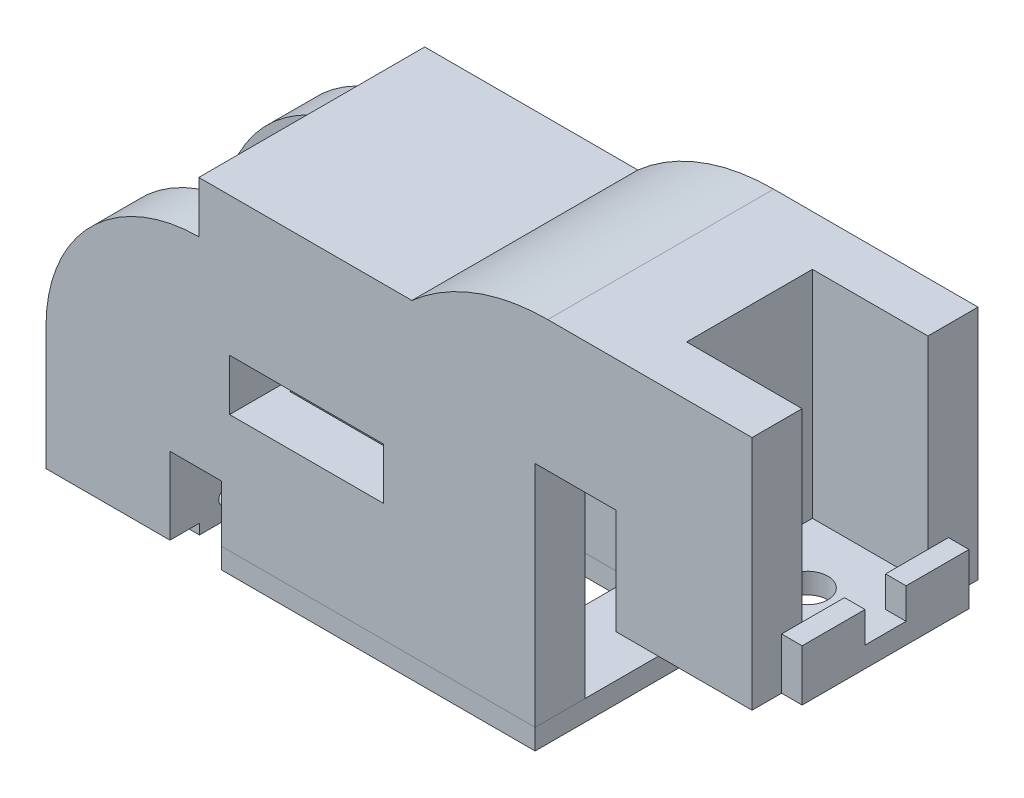
SolidWorks part; units mm, degrees
other "Markup1"
sketch "Sketch12" plane through (-23.815, 32, -11) normal (0, 1, 0) x (1, 0, 0)
ref_plane "Front Plane" through (0, 0, 0) normal (0, 0, 1) x (1, 0, 0)
ref_plane "Top Plane" through (0, 0, 0) normal (0, 1, 0) x (1, 0, 0)
ref_plane "Right Plane" through (0, 0, 0) normal (1, 0, 0) x (0, 0, -1)
sketch "Sketch1" plane through (0, 0, 0) normal (0, 1, 0) x (1, 0, 0)
  line L1 (23.815, -11) -> (-23.815, -11)
  line L2 (23.815, -11) -> (23.815, 11)
  line L3 (23.815, 11) -> (-23.815, 11)
  line L4 (-23.815, -11) -> (-23.815, 11)
  line L5 (23.815, -11) -> (-23.815, 11) construction
  line L6 (23.815, 11) -> (-23.815, -11) construction
  line L7 (10.69, 6.125) -> (15.94, 6.125)
  line L8 (10.69, 6.125) -> (10.69, -6.125)
  line L9 (10.69, -6.125) -> (15.94, -6.125)
  line L10 (15.94, 6.125) -> (15.94, -6.125)
  point P0 (0, 0)
  point P10 (15.94, 0)
  point P11 (23.815, 0)
  point P13 (13.315, 6.125)
  dimension "D1" = 22
  dimension "D2" = 47.63
  dimension "D3" = 10.5
  dimension "D4" = 12.25
  dimension "D5" = 5.25
extrude "Boss-Extrude1" add sketch "Sketch1" along normal blind 2
sketch "Sketch2" plane through (0, 2, 0) normal (0, 1, 0) x (1, 0, 0)
  line L0 (23.815, -11) -> (23.815, 11) construction
  line L1 (-4.935, 6.125) -> (23.815, 6.125)
  line L2 (-4.935, 6.125) -> (-4.935, -6.125)
  line L3 (-4.935, -6.125) -> (23.815, -6.125)
  line L4 (23.815, 6.125) -> (23.815, -6.125)
  point P6 (23.815, 0)
  dimension "D1" = 28.75
  dimension "D2" = 12.25
sketch "Sketch3" plane through (0, 2, 0) normal (0, 1, 0) x (1, 0, 0)
  line L0 (23.815, -11) -> (23.815, 11) construction
  line L1 (-8.935, 11) -> (23.815, 11)
  line L2 (-8.935, 11) -> (-8.935, -11)
  line L3 (-8.935, -11) -> (23.815, -11)
  line L4 (23.815, 11) -> (23.815, -11)
  line L5 (-4.935, 6.125) -> (-4.935, -6.125) construction
  line L8 (23.815, 11) -> (-23.815, 11) construction
  line L9 (-23.815, -11) -> (23.815, -11) construction
  dimension "D1" = 4
extrude "Boss-Extrude2" add sketch "Sketch3" along normal blind 30
extrude "Cut-Extrude1" cut sketch "Sketch2" along normal blind 22.25 contours L3 L4 L1 L2
sketch "Sketch18" plane through (0, 2, 0) normal (0, 1, 0) x (1, 0, 0)
  line L0 (-23.815, 11) -> (-23.815, -11) construction
  line L1 (-23.815, 6.125) -> (-12.565, 6.125)
  line L2 (-23.815, 6.125) -> (-23.815, -6.125)
  line L3 (-23.815, -6.125) -> (-12.565, -6.125)
  line L4 (-12.565, 6.125) -> (-12.565, -6.125)
  line L5 (-8.935, 11) -> (-8.935, -11) construction
  line L6 (-23.815, 11) -> (-8.935, 11)
  line L7 (-23.815, 11) -> (-23.815, -11)
  line L8 (-23.815, -11) -> (-8.935, -11)
  line L9 (-8.935, 11) -> (-8.935, -11)
  circle A0 centre (-18.19, 0) radius 2
  point P6 (-12.565, 0)
  point P12 (-18.19, 6.125)
  line M10 (-8.935, -11) -> (-8.935, 11)
  line M11 (-8.935, 11) -> (-23.815, 11)
  line M12 (-23.815, 11) -> (-23.815, -11)
  line M13 (-23.815, -11) -> (-8.935, -11)
  dimension "D3" = 4
  dimension "D1" = 12.25
  dimension "D2" = 11.25
extrude "Boss-Extrude7" add sketch "Sketch18" along normal blind 25 contours L1 L4 L3 M12 M13 M10 M11 region at (-23.5494, 2, -8.5625)
sketch "Sketch19" plane through (-23.815, 0, 0) normal (-1, 0, 0) x (0, 0, 1)
  line L0 (-11, 0) -> (11, 0) construction
  line L1 (-8.125, 2) -> (8.125, 2)
  line L2 (-8.125, 2) -> (-8.125, 0)
  line L3 (-8.125, 0) -> (8.125, 0)
  line L4 (8.125, 2) -> (8.125, 0)
  line L7 (-6.125, 2) -> (6.125, 2) construction
  line L8 (-6.125, 27) -> (-6.125, 2) construction
  line L9 (6.125, 27) -> (6.125, 2) construction
  dimension "D1" = 2
  dimension "D2" = 2
extrude "Boss-Extrude8" add sketch "Sketch19" along normal blind 2
sketch "Sketch20" plane through (0, 2, 0) normal (0, 1, 0) x (1, 0, 0)
  line L1 (-25.815, 8.125) -> (-23.815, 8.125)
  line L2 (-25.815, 8.125) -> (-25.815, -8.125)
  line L3 (-25.815, -8.125) -> (-23.815, -8.125)
  line L4 (-23.815, 8.125) -> (-23.815, -8.125)
extrude "Boss-Extrude9" add sketch "Sketch20" along normal blind 3
sketch "Sketch39" plane through (-25.815, 0, 0) normal (-1, 0, 0) x (0, 0, 1)
  line L0 (-6.125, 27) -> (-6.125, 5) construction
  line L1 (-6.125, 27) -> (-6.125, 5)
  line L2 (-8.125, 5) -> (8.125, 5) construction
  line L3 (-2, 5) -> (2, 5)
  line L4 (-2, 5) -> (-2, 2)
  line L5 (-2, 2) -> (2, 2)
  line L8 (0, -55) -> (0, 55) construction
  line L9 (2, 5) -> (2, 2)
  line L11 (6.125, 2) -> (-6.125, 2) construction
  line L12 (6.125, 2) -> (-6.125, 2)
  line M9 (-8.125, 0) -> (8.125, 0)
  line M13 (8.125, 5) -> (-8.125, 5)
  dimension "D1" = 4.125
extrude "Cut-Extrude16" cut sketch "Sketch39" against normal blind 2 contours L9 L4 M13 M9 region at (-25.815, 3.5, 0)
sketch "Sketch24" plane through (-25.815, 0, 0) normal (-1, 0, 0) x (0, 0, 1)
  line L0 (-8.125, 0) -> (8.125, 0) construction
  line L2 (-8.125, 0) -> (-8.125, -1)
  line L3 (-8.125, -1) -> (-4.875, -1)
  line L4 (-4.875, 0) -> (-4.875, -1)
  line L16 (0, -55) -> (0, 55) construction
  line L18 (-8.125, 0) -> (-8.125, 0.25)
  line L19 (-8.125, 0.25) -> (-4.875, 0.25)
  line L20 (-4.875, 0) -> (-4.875, 0.25)
  line L21 (8.125, 0) -> (8.125, 0.25)
  line L22 (8.125, 0.25) -> (4.875, 0.25)
  line L23 (4.875, 0) -> (4.875, 0.25)
  line L24 (4.875, 0) -> (4.875, -1)
  line L25 (8.125, -1) -> (4.875, -1)
  line L26 (8.125, 0) -> (8.125, -1)
  dimension "D1" = 1
  dimension "D2" = 3.25
  dimension "D3" = 0.25
extrude "Boss-Extrude11" add sketch "Sketch24" against normal blind 28.03
sketch "Sketch10" plane through (0, 0, 0) normal (0, -1, 0) x (1, 0, 0)
  line L0 (-23.815, 11) -> (23.815, 11) construction
  line L1 (-6.745, 11) -> (-11.745, 11)
  line L2 (-6.745, 11) -> (-6.745, -11)
  line L3 (-6.745, -11) -> (-11.745, -11)
  line L4 (-11.745, 11) -> (-11.745, -11)
  line L5 (23.815, -11) -> (-23.815, -11) construction
  line L6 (-4.935, -6.125) -> (-4.935, 6.125) construction
  line L7 (-4.935, -6.125) -> (-4.935, 6.125)
  line M3 (23.815, 11) -> (-23.815, 11)
  line M11 (-23.815, -11) -> (23.815, -11)
  line M35 (-23.815, 8.125) -> (2.215, 8.125)
  line M37 (2.215, -8.125) -> (-23.815, -8.125)
  line M39 (2.215, 4.875) -> (-25.815, 4.875)
  line M40 (-25.815, -4.875) -> (2.215, -4.875)
  dimension "D1" = 5
  dimension "D2" = 1.81
extrude "Cut-Extrude6" cut sketch "Sketch10" against normal blind 7.5 contours L4 L3 L2 L1
sketch "Sketch21" plane through (-6.745, 0, 0) normal (-1, 0, 0) x (0, 0, 1)
  line L0 (0, -18.15) -> (0, 18.15) construction
  line L1 (11, 0) -> (8.125, 0) construction
  line L2 (11, 7.5) -> (11, 0) construction
  circle A1 centre (5.5, 1) radius 0.75
  circle A2 centre (-5.5, 1) radius 0.75
  dimension "D4" = 1.5
  dimension "D1" = 5.5
  dimension "D2" = 1
extrude "Cut-Extrude12" cut sketch "Sketch21" against normal blind 10
extrude "Cut-Extrude13" cut sketch "Sketch21<5>" along normal through all
sketch "Sketch21<5>" plane through (-6.745, 0, 0) normal (-1, 0, 0) x (0, 0, 1) same geometry as "Sketch21"
extrude "Cut-Extrude14" cut sketch "Sketch10<3>" along normal through all contours L4 L2 M37 M11 | L4 L2 M40 M37 | L4 L2 M39 M40 | L4 L2 M35 M39 | L4 L2 M3 M35 region at (-9.245, 0, 9.5625) region at (-9.245, 0, 6.5) region at (-9.245, 0, 0) region at (-9.245, 0, -6.5) region at (-9.245, 0, -9.5625)
sketch "Sketch10<3>" plane through (0, 0, 0) normal (0, -1, 0) x (1, 0, 0) same geometry as "Sketch10"
sketch "Sketch25" plane through (0, 0, 11) normal (0, 0, 1) x (1, 0, 0)
  line L1 (-5.935, 18.5) -> (9.065, 18.5)
  line L2 (-5.935, 18.5) -> (-5.935, 13.5)
  line L3 (-5.935, 13.5) -> (9.065, 13.5)
  line L4 (9.065, 18.5) -> (9.065, 13.5)
  line L6 (23.815, 32) -> (23.815, 0) construction
  line L7 (-4.935, 24.25) -> (-4.935, 2) construction
  line L8 (-4.935, 24.25) -> (-4.935, 2)
  point P8 (9.065, 16)
  point P13 (23.815, 16)
  dimension "D1" = 5
  dimension "D2" = 15
  dimension "D3" = 1
extrude "Cut-Extrude15" cut sketch "Sketch25" against normal through all contours L1 L8 L3 L4 | L8 L1 L2 L3 region at (-5.435, 16, 11) region at (2.065, 16, 11)
fillet "Fillet2" radius 15 1 edges at (-23.815, 27, 8.5625)
sketch "Sketch29" plane through (0, 32, 0) normal (0, 1, 0) x (1, 0, 0)
  line L0 (23.815, 11) -> (-8.935, 11) construction
  line L1 (23.815, -11) -> (33.69, -11)
  line L2 (23.815, -11) -> (23.815, 11)
  line L3 (23.815, 11) -> (33.69, 11)
  line L4 (33.69, -11) -> (33.69, 11)
  line L5 (-8.935, -11) -> (23.815, -11) construction
  line L6 (23.815, -11) -> (23.815, 11) construction
  dimension "D1" = 9.875
extrude "Boss-Extrude12" add sketch "Sketch29" against normal blind 7.75 contours L3 L4 L1 L2
sketch "Sketch30" plane through (0, 32, 0) normal (0, 1, 0) x (1, 0, 0)
  line L0 (33.69, -11) -> (33.69, 11) construction
  line L1 (33.69, 11) -> (44.94, 11)
  line L2 (33.69, 6.125) -> (33.69, -6.125)
  line L3 (33.69, -11) -> (44.94, -11)
  line L4 (44.94, 11) -> (44.94, -11)
  line L5 (33.69, 11) -> (-8.935, 11) construction
  line L6 (-8.935, -11) -> (33.69, -11) construction
  line L8 (33.69, 6.125) -> (44.94, 6.125)
  line L9 (33.69, 6.125) -> (33.69, -6.125)
  line L10 (33.69, -6.125) -> (44.94, -6.125)
  line L11 (44.94, 6.125) -> (44.94, -6.125)
  line L12 (31.69, 11) -> (33.69, 11)
  line L13 (31.69, 11) -> (31.69, -11)
  line L14 (31.69, -11) -> (33.69, -11)
  line L15 (33.69, 6.125) -> (33.69, -6.125)
  circle A0 centre (39.315, 0) radius 2
  point P12 (33.69, 0)
  point P13 (39.315, 11)
  point P14 (44.94, 0)
  line M4 (-8.935, -11) -> (33.69, -11)
  line M5 (33.69, -11) -> (33.69, 11)
  line M6 (33.69, 11) -> (-8.935, 11)
  dimension "D1" = 11.25
  dimension "D2" = 4
  dimension "D3" = 12.25
  dimension "D4" = 2
extrude "Boss-Extrude13" add sketch "Sketch30" against normal blind 16 contours L13 M6 M4 M5 | L8 L4 L1 M5 | L10 L3 L4 M5 region at (32.69, 32, 0) region at (39.315, 32, -8.5625) region at (39.315, 32, 8.5625)
sketch "Sketch36" plane through (0, 16, 0) normal (0, -1, 0) x (1, 0, 0)
  line L11 (44.94, 11) -> (31.69, 11)
  line L12 (44.94, 11) -> (44.94, -11)
  line L13 (44.94, -11) -> (31.69, -11)
  line L14 (31.69, 11) -> (31.69, -11)
  line L15 (33.69, 6.125) -> (44.94, 6.125) construction
  circle A0 centre (39.315, 0) radius 2
  dimension "D1" = 4
  dimension "D2" = 5.625
  dimension "D3" = 6.125
extrude "Boss-Extrude16" add sketch "Sketch36" along normal blind 2
sketch "Sketch38" plane through (44.94, 0, 0) normal (1, 0, 0) x (0, 0, -1)
  line L17 (-8.125, 19) -> (-2, 19)
  line L18 (-8.125, 19) -> (-8.125, 14)
  line L19 (-8.125, 14) -> (8.125, 14)
  line L20 (-2, 19) -> (-2, 16)
  line L21 (-6.125, 16) -> (-6.125, 32) construction
  line L22 (6.125, 16) -> (-6.125, 16) construction
  line L23 (11, 14) -> (-11, 14) construction
  line L31 (-2, 16) -> (2, 16)
  line L33 (0, 18.15) -> (0, -18.15) construction
  line L34 (2, 19) -> (2, 16)
  line L35 (8.125, 19) -> (2, 19)
  line L36 (8.125, 19) -> (8.125, 14)
  dimension "D1" = 2
  dimension "D2" = 3
  dimension "D3" = 4.125
extrude "Boss-Extrude18" add sketch "Sketch30<4>" along normal blind 5 contours L8 L4 L1 M5 | L13 M6 M4 M5 | L10 L3 L4 M5 region at (32.69, 32, 0) region at (39.315, 32, -8.5625) region at (39.315, 32, 8.5625)
sketch "Sketch30<4>" plane through (0, 32, 0) normal (0, 1, 0) x (1, 0, 0) same geometry as "Sketch30"
extrude "Boss-Extrude19" add sketch "Sketch38" along normal blind 2
extrude "Boss-Extrude20" add sketch "Sketch29<3>" along normal blind 5
sketch "Sketch29<3>" plane through (0, 32, 0) normal (0, 1, 0) x (1, 0, 0) same geometry as "Sketch29"
sketch "Sketch40" plane through (0, 32, 0) normal (0, 1, 0) x (1, 0, 0)
  line L0 (-8.935, -11) -> (23.815, -11) construction
  line L1 (23.815, 11) -> (11.815, 11)
  line L2 (23.815, 11) -> (23.815, -11)
  line L3 (23.815, -11) -> (11.815, -11)
  line L4 (11.815, 11) -> (11.815, -11)
  dimension "D1" = 12
extrude "Boss-Extrude21" add sketch "Sketch40" along normal blind 5
fillet "Fillet5" radius 20 1 edges at (11.815, 37, 0)
sketch "Sketch44" plane through (0, 0, 11) normal (0, 0, 1) x (1, 0, 0)
  line L0 (-6.745, 2) -> (23.815, 2)
  line L1 (-6.745, 7.5) -> (-6.745, 0) construction
  line L2 (23.815, 24.25) -> (23.815, 0) construction
  line L3 (-6.745, 0) -> (23.815, 0) construction
  dimension "D1" = 2
split "Split2" trim tools "Sketch44" bodies to split 134 resulting bodies 139 140
sketch "Sketch45" plane through (0, 2, 0) normal (0, 1, 0) x (1, 0, 0)
  line L0 (-25.815, 2) -> (-25.815, -2) construction
  line L1 (-23.815, -6.125) -> (-12.565, -6.125) construction
  circle A0 centre (-18.19, 0) radius 2
  point P5 (-25.815, 0)
  point P9 (-18.19, -6.125)
  dimension "D1" = 4
extrude "Cut-Extrude17" cut sketch "Sketch45" against normal through all
